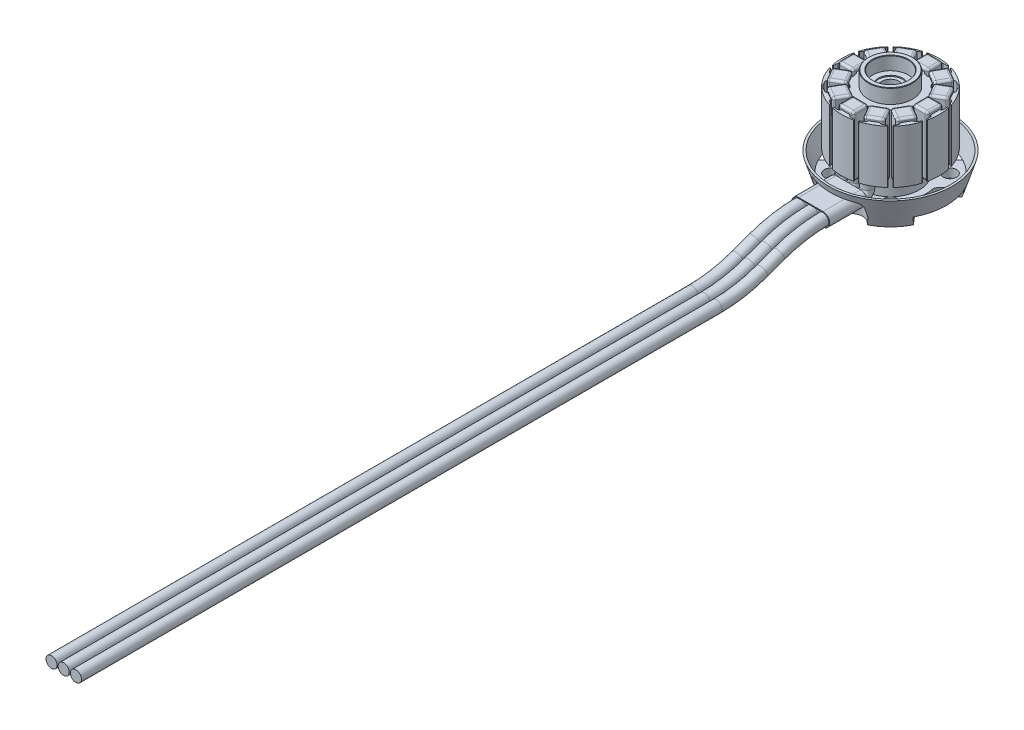
SolidWorks part; units mm, degrees
ref_plane "Front Plane" through (0, 0, 0) normal (0, 0, 1) x (1, 0, 0)
ref_plane "Top Plane" through (0, 0, 0) normal (0, 1, 0) x (1, 0, 0)
ref_plane "Right Plane" through (0, 0, 0) normal (1, 0, 0) x (0, 0, -1)
ref_plane "Plane6" through (0, 0, 15.3597) normal (0, 0, 1) x (1, 0, 0)
sketch "Sketch1" plane through (0, 0, 0) normal (0, 0, 1) x (1, 0, 0)
  line L0 (4, 0) -> (12, 0)
  line L1 (12, 0) -> (14, 6.5)
  line L2 (14, 6.5) -> (13.5, 6.5)
  line L3 (4, 0) -> (4, 3)
  line L4 (2, 3.35) -> (2.1, 3.25)
  line L5 (5, 7) -> (5, 22.15)
  line L6 (6.5, 2) -> (12.1154, 2)
  line L7 (13.5, 6.5) -> (12.1154, 2)
  line L14 (4.9, 22.25) -> (4.1, 22.25)
  line L15 (4, 22.15) -> (4, 19.25)
  line L16 (4, 19.25) -> (2.75, 19.25)
  line L17 (2, 3.35) -> (2, 19)
  line L18 (0, -5) -> (0, 30) construction
  line L19 (2.1, 3.25) -> (2.75, 3.25)
  line L20 (4.1, 22.25) -> (4, 22.15)
  line L21 (5, 22.15) -> (4.9, 22.25)
  line L23 (2.85, 3) -> (4, 3)
  line L24 (2, 19) -> (2.75, 19)
  line L25 (5, 7) -> (6.5, 7)
  line L26 (6.5, 7) -> (6.5, 2)
  line L27 (2.75, 19) -> (2.75, 19.25)
  line L28 (2.75, 3.25) -> (2.75, 3.1)
  line L29 (2.75, 3.1) -> (2.85, 3)
  point P9 (5, 22.25)
  point P22 (4, 22.25)
  point P24 (2, 3.25)
  point P44 (2.75, 3)
revolve "Revolve1" add sketch "Sketch1" angle 360 about L18
ref_plane "Plane1" through (0, 0, 15) normal (0, 0, 1) x (1, 0, 0)
sketch "Sketch5" plane through (0, 7, 0) normal (0, 1, 0) x (1, 0, 0)
  line L0 (-1, 9.8636) -> (-1, 7.3485)
  line L1 (0, 0) -> (0, 14) construction
  line L2 (-2.2472, 10.3636) -> (-1.5, 10.3636)
  line L3 (2.2472, 10.3636) -> (1.5, 10.3636)
  line L4 (1, 9.8636) -> (1, 7.3485)
  line L5 (7.1279, 7.8516) -> (6.4808, 8.2252)
  line L6 (5.7978, 8.0421) -> (4.5403, 5.864)
  line L7 (4.0658, 9.0421) -> (2.8082, 6.864)
  line L8 (3.2357, 10.0988) -> (3.8828, 9.7252)
  line L9 (10.0988, 3.2357) -> (9.7252, 3.8828)
  line L10 (9.0421, 4.0658) -> (6.864, 2.8082)
  line L11 (8.0421, 5.7978) -> (5.864, 4.5403)
  line L12 (7.8516, 7.1279) -> (8.2252, 6.4808)
  line L13 (10.3636, -2.2472) -> (10.3636, -1.5)
  line L14 (9.8636, -1) -> (7.3485, -1)
  line L15 (9.8636, 1) -> (7.3485, 1)
  line L16 (10.3636, 2.2472) -> (10.3636, 1.5)
  line L17 (7.8516, -7.1279) -> (8.2252, -6.4808)
  line L18 (8.0421, -5.7978) -> (5.864, -4.5403)
  line L19 (9.0421, -4.0658) -> (6.864, -2.8082)
  line L20 (10.0988, -3.2357) -> (9.7252, -3.8828)
  line L21 (3.2357, -10.0988) -> (3.8828, -9.7252)
  line L22 (4.0658, -9.0421) -> (2.8082, -6.864)
  line L23 (5.7978, -8.0421) -> (4.5403, -5.864)
  line L24 (7.1279, -7.8516) -> (6.4808, -8.2252)
  line L25 (-2.2472, -10.3636) -> (-1.5, -10.3636)
  line L26 (-1, -9.8636) -> (-1, -7.3485)
  line L27 (1, -9.8636) -> (1, -7.3485)
  line L28 (2.2472, -10.3636) -> (1.5, -10.3636)
  line L29 (-7.1279, -7.8516) -> (-6.4808, -8.2252)
  line L30 (-5.7978, -8.0421) -> (-4.5403, -5.864)
  line L31 (-4.0658, -9.0421) -> (-2.8082, -6.864)
  line L32 (-3.2357, -10.0988) -> (-3.8828, -9.7252)
  line L33 (-10.0988, -3.2357) -> (-9.7252, -3.8828)
  line L34 (-9.0421, -4.0658) -> (-6.864, -2.8082)
  line L35 (-8.0421, -5.7978) -> (-5.864, -4.5403)
  line L36 (-7.8516, -7.1279) -> (-8.2252, -6.4808)
  line L37 (-10.3636, 2.2472) -> (-10.3636, 1.5)
  line L38 (-9.8636, 1) -> (-7.3485, 1)
  line L39 (-9.8636, -1) -> (-7.3485, -1)
  line L40 (-10.3636, -2.2472) -> (-10.3636, -1.5)
  line L41 (-7.8516, 7.1279) -> (-8.2252, 6.4808)
  line L42 (-8.0421, 5.7978) -> (-5.864, 4.5403)
  line L43 (-9.0421, 4.0658) -> (-6.864, 2.8082)
  line L44 (-10.0988, 3.2357) -> (-9.7252, 3.8828)
  line L45 (-3.2357, 10.0988) -> (-3.8828, 9.7252)
  line L46 (-4.0658, 9.0421) -> (-2.8082, 6.864)
  line L47 (-5.7978, 8.0421) -> (-4.5403, 5.864)
  line L48 (-7.1279, 7.8516) -> (-6.4808, 8.2252)
  circle A0 centre (0, 0) radius 5
  arc A1 (2.2888, 10.7592) -> (-2.2888, 10.7592) centre (0, 0) ccw
  arc A2 (-1.4, 6.8586) -> (-2.2169, 6.6397) centre (0, 0) ccw
  arc A3 (-2.2472, 10.3636) -> (-2.2888, 10.7592) centre (-2.2472, 10.5636) cw
  arc A4 (-1.5, 10.3636) -> (-1, 9.8636) centre (-1.5, 9.8636) cw
  arc A5 (-1, 7.3485) -> (-1.4, 6.8586) centre (-1.5, 7.3485) cw
  arc A6 (2.2472, 10.3636) -> (2.2888, 10.7592) centre (2.2472, 10.5636) ccw
  arc A7 (1.5, 10.3636) -> (1, 9.8636) centre (1.5, 9.8636) ccw
  arc A8 (1, 7.3485) -> (1.4, 6.8586) centre (1.5, 7.3485) ccw
  arc A9 (7.3618, 8.1734) -> (3.3975, 10.4622) centre (0, 0) ccw
  arc A10 (6.4808, 8.2252) -> (5.7978, 8.0421) centre (6.2308, 7.7921) ccw
  arc A11 (7.1279, 7.8516) -> (7.3618, 8.1734) centre (7.2279, 8.0248) ccw
  arc A12 (4.5403, 5.864) -> (4.6417, 5.2397) centre (4.9733, 5.614) ccw
  arc A13 (2.8082, 6.864) -> (2.2169, 6.6397) centre (2.3752, 7.114) cw
  arc A14 (3.8828, 9.7252) -> (4.0658, 9.0421) centre (3.6328, 9.2921) cw
  arc A15 (3.2357, 10.0988) -> (3.3975, 10.4622) centre (3.3357, 10.272) cw
  arc A16 (10.4622, 3.3975) -> (8.1734, 7.3618) centre (0, 0) ccw
  arc A17 (9.7252, 3.8828) -> (9.0421, 4.0658) centre (9.2921, 3.6328) ccw
  arc A18 (10.0988, 3.2357) -> (10.4622, 3.3975) centre (10.272, 3.3357) ccw
  arc A19 (6.864, 2.8082) -> (6.6397, 2.2169) centre (7.114, 2.3752) ccw
  arc A20 (5.864, 4.5403) -> (5.2397, 4.6417) centre (5.614, 4.9733) cw
  arc A21 (8.2252, 6.4808) -> (8.0421, 5.7978) centre (7.7921, 6.2308) cw
  arc A22 (7.8516, 7.1279) -> (8.1734, 7.3618) centre (8.0248, 7.2279) cw
  arc A23 (10.7592, -2.2888) -> (10.7592, 2.2888) centre (0, 0) ccw
  arc A24 (10.3636, -1.5) -> (9.8636, -1) centre (9.8636, -1.5) ccw
  arc A25 (10.3636, -2.2472) -> (10.7592, -2.2888) centre (10.5636, -2.2472) ccw
  arc A26 (7.3485, -1) -> (6.8586, -1.4) centre (7.3485, -1.5) ccw
  arc A27 (7.3485, 1) -> (6.8586, 1.4) centre (7.3485, 1.5) cw
  arc A28 (10.3636, 1.5) -> (9.8636, 1) centre (9.8636, 1.5) cw
  arc A29 (10.3636, 2.2472) -> (10.7592, 2.2888) centre (10.5636, 2.2472) cw
  arc A30 (8.1734, -7.3618) -> (10.4622, -3.3975) centre (0, 0) ccw
  arc A31 (8.2252, -6.4808) -> (8.0421, -5.7978) centre (7.7921, -6.2308) ccw
  arc A32 (7.8516, -7.1279) -> (8.1734, -7.3618) centre (8.0248, -7.2279) ccw
  arc A33 (5.864, -4.5403) -> (5.2397, -4.6417) centre (5.614, -4.9733) ccw
  arc A34 (6.864, -2.8082) -> (6.6397, -2.2169) centre (7.114, -2.3752) cw
  arc A35 (9.7252, -3.8828) -> (9.0421, -4.0658) centre (9.2921, -3.6328) cw
  arc A36 (10.0988, -3.2357) -> (10.4622, -3.3975) centre (10.272, -3.3357) cw
  arc A37 (3.3975, -10.4622) -> (7.3618, -8.1734) centre (0, 0) ccw
  arc A38 (3.8828, -9.7252) -> (4.0658, -9.0421) centre (3.6328, -9.2921) ccw
  arc A39 (3.2357, -10.0988) -> (3.3975, -10.4622) centre (3.3357, -10.272) ccw
  arc A40 (2.8082, -6.864) -> (2.2169, -6.6397) centre (2.3752, -7.114) ccw
  arc A41 (4.5403, -5.864) -> (4.6417, -5.2397) centre (4.9733, -5.614) cw
  arc A42 (6.4808, -8.2252) -> (5.7978, -8.0421) centre (6.2308, -7.7921) cw
  arc A43 (7.1279, -7.8516) -> (7.3618, -8.1734) centre (7.2279, -8.0248) cw
  arc A44 (-2.2888, -10.7592) -> (2.2888, -10.7592) centre (0, 0) ccw
  arc A45 (-1.5, -10.3636) -> (-1, -9.8636) centre (-1.5, -9.8636) ccw
  arc A46 (-2.2472, -10.3636) -> (-2.2888, -10.7592) centre (-2.2472, -10.5636) ccw
  arc A47 (-1, -7.3485) -> (-1.4, -6.8586) centre (-1.5, -7.3485) ccw
  arc A48 (1, -7.3485) -> (1.4, -6.8586) centre (1.5, -7.3485) cw
  arc A49 (1.5, -10.3636) -> (1, -9.8636) centre (1.5, -9.8636) cw
  arc A50 (2.2472, -10.3636) -> (2.2888, -10.7592) centre (2.2472, -10.5636) cw
  arc A51 (-7.3618, -8.1734) -> (-3.3975, -10.4622) centre (0, 0) ccw
  arc A52 (-6.4808, -8.2252) -> (-5.7978, -8.0421) centre (-6.2308, -7.7921) ccw
  arc A53 (-7.1279, -7.8516) -> (-7.3618, -8.1734) centre (-7.2279, -8.0248) ccw
  arc A54 (-4.5403, -5.864) -> (-4.6417, -5.2397) centre (-4.9733, -5.614) ccw
  arc A55 (-2.8082, -6.864) -> (-2.2169, -6.6397) centre (-2.3752, -7.114) cw
  arc A56 (-3.8828, -9.7252) -> (-4.0658, -9.0421) centre (-3.6328, -9.2921) cw
  arc A57 (-3.2357, -10.0988) -> (-3.3975, -10.4622) centre (-3.3357, -10.272) cw
  arc A58 (-10.4622, -3.3975) -> (-8.1734, -7.3618) centre (0, 0) ccw
  arc A59 (-9.7252, -3.8828) -> (-9.0421, -4.0658) centre (-9.2921, -3.6328) ccw
  arc A60 (-10.0988, -3.2357) -> (-10.4622, -3.3975) centre (-10.272, -3.3357) ccw
  arc A61 (-6.864, -2.8082) -> (-6.6397, -2.2169) centre (-7.114, -2.3752) ccw
  arc A62 (-5.864, -4.5403) -> (-5.2397, -4.6417) centre (-5.614, -4.9733) cw
  arc A63 (-8.2252, -6.4808) -> (-8.0421, -5.7978) centre (-7.7921, -6.2308) cw
  arc A64 (-7.8516, -7.1279) -> (-8.1734, -7.3618) centre (-8.0248, -7.2279) cw
  arc A65 (-10.7592, 2.2888) -> (-10.7592, -2.2888) centre (0, 0) ccw
  arc A66 (-10.3636, 1.5) -> (-9.8636, 1) centre (-9.8636, 1.5) ccw
  arc A67 (-10.3636, 2.2472) -> (-10.7592, 2.2888) centre (-10.5636, 2.2472) ccw
  arc A68 (-7.3485, 1) -> (-6.8586, 1.4) centre (-7.3485, 1.5) ccw
  arc A69 (-7.3485, -1) -> (-6.8586, -1.4) centre (-7.3485, -1.5) cw
  arc A70 (-10.3636, -1.5) -> (-9.8636, -1) centre (-9.8636, -1.5) cw
  arc A71 (-10.3636, -2.2472) -> (-10.7592, -2.2888) centre (-10.5636, -2.2472) cw
  arc A72 (-8.1734, 7.3618) -> (-10.4622, 3.3975) centre (0, 0) ccw
  arc A73 (-8.2252, 6.4808) -> (-8.0421, 5.7978) centre (-7.7921, 6.2308) ccw
  arc A74 (-7.8516, 7.1279) -> (-8.1734, 7.3618) centre (-8.0248, 7.2279) ccw
  arc A75 (-5.864, 4.5403) -> (-5.2397, 4.6417) centre (-5.614, 4.9733) ccw
  arc A76 (-6.864, 2.8082) -> (-6.6397, 2.2169) centre (-7.114, 2.3752) cw
  arc A77 (-9.7252, 3.8828) -> (-9.0421, 4.0658) centre (-9.2921, 3.6328) cw
  arc A78 (-10.0988, 3.2357) -> (-10.4622, 3.3975) centre (-10.272, 3.3357) cw
  arc A79 (-3.3975, 10.4622) -> (-7.3618, 8.1734) centre (0, 0) ccw
  arc A80 (-3.8828, 9.7252) -> (-4.0658, 9.0421) centre (-3.6328, 9.2921) ccw
  arc A81 (-3.2357, 10.0988) -> (-3.3975, 10.4622) centre (-3.3357, 10.272) ccw
  arc A82 (-2.8082, 6.864) -> (-2.2169, 6.6397) centre (-2.3752, 7.114) ccw
  arc A83 (-4.5403, 5.864) -> (-4.6417, 5.2397) centre (-4.9733, 5.614) cw
  arc A84 (-6.4808, 8.2252) -> (-5.7978, 8.0421) centre (-6.2308, 7.7921) cw
  arc A85 (-7.1279, 7.8516) -> (-7.3618, 8.1734) centre (-7.2279, 8.0248) cw
  arc A86 (-4.6417, 5.2397) -> (-5.2397, 4.6417) centre (0, 0) ccw
  arc A87 (2.2169, 6.6397) -> (1.4, 6.8586) centre (0, 0) ccw
  arc A88 (5.2397, 4.6417) -> (4.6417, 5.2397) centre (0, 0) ccw
  arc A89 (6.8586, 1.4) -> (6.6397, 2.2169) centre (0, 0) ccw
  arc A90 (6.6397, -2.2169) -> (6.8586, -1.4) centre (0, 0) ccw
  arc A91 (-6.6397, 2.2169) -> (-6.8586, 1.4) centre (0, 0) ccw
  arc A92 (-6.8586, -1.4) -> (-6.6397, -2.2169) centre (0, 0) ccw
  arc A93 (-5.2397, -4.6417) -> (-4.6417, -5.2397) centre (0, 0) ccw
  arc A94 (-2.2169, -6.6397) -> (-1.4, -6.8586) centre (0, 0) ccw
  arc A95 (1.4, -6.8586) -> (2.2169, -6.6397) centre (0, 0) ccw
  arc A96 (4.6417, -5.2397) -> (5.2397, -4.6417) centre (0, 0) ccw
  point P223 (0, 0)
  dimension "D1" = 22
  dimension "D2" = 0.2
  dimension "D3" = 0.5
  dimension "D4" = 7
  dimension "D7" = 10
  dimension "D5" = 1
  dimension "D6" = 12
sketch "Sketch6" plane through (0, 0, 0) normal (0, -1, 0) x (1, 0, 0)
  line L0 (-14.1421, 14.1421) -> (0, 0) construction
  line L1 (0, 0) -> (14.1421, 14.1421) construction
  line L2 (0, 0) -> (0, 28.2843) construction
  line L3 (-7.1141, 12.0577) -> (-4.8767, 10.14)
  line L4 (7.1141, 12.0577) -> (4.8767, 10.14)
  line L5 (12.0577, 7.1141) -> (8.0592, 2.4492)
  line L6 (12.0577, -7.1141) -> (8.0592, -2.4492)
  line L7 (7.1141, -12.0577) -> (2.4492, -8.0592)
  line L8 (-7.1141, -12.0577) -> (-2.4492, -8.0592)
  line L9 (-12.0577, -7.1141) -> (-8.0592, -2.4492)
  line L10 (-12.0577, 7.1141) -> (-8.0592, 2.4492)
  line L11 (0, 12) -> (-0.7499, 12.0123)
  line L12 (0, 12) -> (0.7499, 12.0123)
  arc A0 (-12.0577, 7.1141) -> (-12.0577, -7.1141) centre (0, 0) ccw
  arc A1 (-1.5986, -7.8387) -> (1.5986, -7.8387) centre (0, 0) ccw
  arc A2 (12.0577, -7.1141) -> (12.0577, 7.1141) centre (0, 0) ccw
  arc A3 (-7.1141, -12.0577) -> (7.1141, -12.0577) centre (0, 0) ccw
  arc A4 (-7.8387, 1.5986) -> (-7.8387, -1.5986) centre (0, 0) ccw
  arc A6 (7.8387, -1.5986) -> (7.8387, 1.5986) centre (0, 0) ccw
  arc A7 (7.1141, 12.0577) -> (-7.1141, 12.0577) centre (0, 0) ccw
  circle A8 centre (-6.7175, 6.7175) radius 1.5
  circle A9 centre (5.6569, 5.6569) radius 1.5
  circle A10 centre (6.7175, -6.7175) radius 1.5
  circle A11 centre (-5.6569, -5.6569) radius 1.5
  arc A12 (-2.4492, -8.0592) -> (-1.5986, -7.8387) centre (-1.7984, -8.8185) cw
  arc A13 (2.4492, -8.0592) -> (1.5986, -7.8387) centre (1.7984, -8.8185) ccw
  arc A14 (8.0592, -2.4492) -> (7.8387, -1.5986) centre (8.8185, -1.7984) cw
  arc A15 (8.0592, 2.4492) -> (7.8387, 1.5986) centre (8.8185, 1.7984) ccw
  arc A17 (4.8767, 10.14) -> (0.7499, 12.0123) centre (3.2498, 12.0381) cw
  arc A18 (-8.0592, 2.4492) -> (-7.8387, 1.5986) centre (-8.8185, 1.7984) cw
  arc A19 (-8.0592, -2.4492) -> (-7.8387, -1.5986) centre (-8.8185, -1.7984) ccw
  arc A20 (-4.8767, 10.14) -> (-0.7499, 12.0123) centre (-3.2498, 12.0381) ccw
  point P20 (0, 0)
  point P39 (2.0641, 7.7291)
  point P42 (-2.0641, 7.7291)
  dimension "D1" = 28
  dimension "D2" = 16
  dimension "D3" = 3
  dimension "D4" = 3
  dimension "D7" = 1
  dimension "D8" = 5
  dimension "D5" = 9.5
  dimension "D6" = 8
  dimension "D9" = 0.75
extrude "Cut-Extrude1" cut sketch "Sketch6" against normal blind 2
ref_axis "Axis2" through (0, 19, 0) along (0, -1, 0)
sketch "Sketch10" plane through (6.2132, 0, 15.3597) normal (0, 0, 1) x (1, 0, 0)
  line L0 (-12.2092, 2) -> (-0.2172, 2) construction
  line L1 (-12.2092, 2) -> (-0.2172, 2)
  line L2 (-12.2092, 2) -> (-12.2092, 4)
  line L3 (-11.2092, 5) -> (-1.2172, 5)
  line L4 (-0.2172, 4) -> (-0.2172, 2)
  arc A0 (-1.2172, 5) -> (-0.2172, 4) centre (-1.2172, 4) cw
  arc A1 (-12.2092, 4) -> (-11.2092, 5) centre (-11.2092, 4) cw
  dimension "D1" = 1
extrude "Cut-Extrude3" cut sketch "Sketch10" against normal blind 5 contours L1 L4 A0 L3 A1 L2
sketch "Sketch11" plane through (0, 7, 0) normal (0, 1, 0) x (1, 0, 0)
  line L0 (-1, 10) -> (-1, 6.8374)
  line L1 (-2.3184, 10.5) -> (-1.5, 10.5)
  line L2 (0, 20) -> (0, 0) construction
  line L3 (0, 0) -> (20, 0) construction
  line L4 (2.3184, 10.5) -> (1.5, 10.5)
  line L5 (1, 10) -> (1, 6.8374)
  line L6 (3.2422, 10.2525) -> (3.951, 9.8433)
  line L7 (4.134, 9.1603) -> (2.5527, 6.4214)
  line L8 (5.866, 8.1603) -> (4.2847, 5.4214)
  line L9 (7.2578, 7.9341) -> (6.549, 8.3433)
  line L10 (7.9341, 7.2578) -> (8.3433, 6.549)
  line L11 (8.1603, 5.866) -> (5.4214, 4.2847)
  line L12 (9.1603, 4.134) -> (6.4214, 2.5527)
  line L13 (10.2525, 3.2422) -> (9.8433, 3.951)
  line L14 (10.5, 2.3184) -> (10.5, 1.5)
  line L15 (10, 1) -> (6.8374, 1)
  line L16 (10, -1) -> (6.8374, -1)
  line L17 (10.5, -2.3184) -> (10.5, -1.5)
  line L18 (10.2525, -3.2422) -> (9.8433, -3.951)
  line L19 (9.1603, -4.134) -> (6.4214, -2.5527)
  line L20 (8.1603, -5.866) -> (5.4214, -4.2847)
  line L21 (7.9341, -7.2578) -> (8.3433, -6.549)
  line L22 (7.2578, -7.9341) -> (6.549, -8.3433)
  line L23 (5.866, -8.1603) -> (4.2847, -5.4214)
  line L24 (4.134, -9.1603) -> (2.5527, -6.4214)
  line L25 (3.2422, -10.2525) -> (3.951, -9.8433)
  line L26 (2.3184, -10.5) -> (1.5, -10.5)
  line L27 (1, -10) -> (1, -6.8374)
  line L28 (-1, -10) -> (-1, -6.8374)
  line L29 (-2.3184, -10.5) -> (-1.5, -10.5)
  line L30 (-3.2422, -10.2525) -> (-3.951, -9.8433)
  line L31 (-4.134, -9.1603) -> (-2.5527, -6.4214)
  line L32 (-5.866, -8.1603) -> (-4.2847, -5.4214)
  line L33 (-7.2578, -7.9341) -> (-6.549, -8.3433)
  line L34 (-7.9341, -7.2578) -> (-8.3433, -6.549)
  line L35 (-8.1603, -5.866) -> (-5.4214, -4.2847)
  line L36 (-9.1603, -4.134) -> (-6.4214, -2.5527)
  line L37 (-10.2525, -3.2422) -> (-9.8433, -3.951)
  line L38 (-10.5, -2.3184) -> (-10.5, -1.5)
  line L39 (-10, -1) -> (-6.8374, -1)
  line L40 (-10, 1) -> (-6.8374, 1)
  line L41 (-10.5, 2.3184) -> (-10.5, 1.5)
  line L42 (-10.2525, 3.2422) -> (-9.8433, 3.951)
  line L43 (-9.1603, 4.134) -> (-6.4214, 2.5527)
  line L44 (-8.1603, 5.866) -> (-5.4214, 4.2847)
  line L45 (-7.9341, 7.2578) -> (-8.3433, 6.549)
  line L46 (-7.2578, 7.9341) -> (-6.549, 8.3433)
  line L47 (-5.866, 8.1603) -> (-4.2847, 5.4214)
  line L48 (-4.134, 9.1603) -> (-2.5527, 6.4214)
  line L49 (-3.2422, 10.2525) -> (-3.951, 9.8433)
  circle A0 centre (0, 0) radius 5
  arc A1 (2.3451, 10.7471) -> (-2.3451, 10.7471) centre (0, 0) ccw
  arc A2 (-1.3929, 6.349) -> (-1.9683, 6.1948) centre (0, 0) ccw
  arc A3 (2.3184, 10.5) -> (2.3451, 10.7471) centre (2.3184, 10.625) ccw
  arc A4 (-2.3184, 10.5) -> (-2.3451, 10.7471) centre (-2.3184, 10.625) cw
  arc A5 (1.5, 10.5) -> (1, 10) centre (1.5, 10) ccw
  arc A6 (-1, 10) -> (-1.5, 10.5) centre (-1.5, 10) ccw
  arc A7 (1, 6.8374) -> (1.3929, 6.349) centre (1.5, 6.8374) ccw
  arc A8 (-1, 6.8374) -> (-1.3929, 6.349) centre (-1.5, 6.8374) cw
  arc A9 (7.4044, 8.1348) -> (3.3427, 10.4798) centre (0, 0) ccw
  arc A10 (3.2422, 10.2525) -> (3.3427, 10.4798) centre (3.3047, 10.3607) cw
  arc A11 (4.134, 9.1603) -> (3.951, 9.8433) centre (3.701, 9.4103) ccw
  arc A12 (2.5527, 6.4214) -> (1.9683, 6.1948) centre (2.1197, 6.6714) cw
  arc A13 (4.2847, 5.4214) -> (4.3808, 4.802) centre (4.7177, 5.1714) ccw
  arc A14 (6.549, 8.3433) -> (5.866, 8.1603) centre (6.299, 7.9103) ccw
  arc A15 (7.2578, 7.9341) -> (7.4044, 8.1348) centre (7.3203, 8.0423) ccw
  arc A16 (10.4798, 3.3427) -> (8.1348, 7.4044) centre (0, 0) ccw
  arc A17 (7.9341, 7.2578) -> (8.1348, 7.4044) centre (8.0423, 7.3203) cw
  arc A18 (8.1603, 5.866) -> (8.3433, 6.549) centre (7.9103, 6.299) ccw
  arc A19 (5.4214, 4.2847) -> (4.802, 4.3808) centre (5.1714, 4.7177) cw
  arc A20 (6.4214, 2.5527) -> (6.1948, 1.9683) centre (6.6714, 2.1197) ccw
  arc A21 (9.8433, 3.951) -> (9.1603, 4.134) centre (9.4103, 3.701) ccw
  arc A22 (10.2525, 3.2422) -> (10.4798, 3.3427) centre (10.3607, 3.3047) ccw
  arc A23 (10.7471, -2.3451) -> (10.7471, 2.3451) centre (0, 0) ccw
  arc A24 (10.5, 2.3184) -> (10.7471, 2.3451) centre (10.625, 2.3184) cw
  arc A25 (10, 1) -> (10.5, 1.5) centre (10, 1.5) ccw
  arc A26 (6.8374, 1) -> (6.349, 1.3929) centre (6.8374, 1.5) cw
  arc A27 (6.8374, -1) -> (6.349, -1.3929) centre (6.8374, -1.5) ccw
  arc A28 (10.5, -1.5) -> (10, -1) centre (10, -1.5) ccw
  arc A29 (10.5, -2.3184) -> (10.7471, -2.3451) centre (10.625, -2.3184) ccw
  arc A30 (8.1348, -7.4044) -> (10.4798, -3.3427) centre (0, 0) ccw
  arc A31 (10.2525, -3.2422) -> (10.4798, -3.3427) centre (10.3607, -3.3047) cw
  arc A32 (9.1603, -4.134) -> (9.8433, -3.951) centre (9.4103, -3.701) ccw
  arc A33 (6.4214, -2.5527) -> (6.1948, -1.9683) centre (6.6714, -2.1197) cw
  arc A34 (5.4214, -4.2847) -> (4.802, -4.3808) centre (5.1714, -4.7177) ccw
  arc A35 (8.3433, -6.549) -> (8.1603, -5.866) centre (7.9103, -6.299) ccw
  arc A36 (7.9341, -7.2578) -> (8.1348, -7.4044) centre (8.0423, -7.3203) ccw
  arc A37 (3.3427, -10.4798) -> (7.4044, -8.1348) centre (0, 0) ccw
  arc A38 (7.2578, -7.9341) -> (7.4044, -8.1348) centre (7.3203, -8.0423) cw
  arc A39 (5.866, -8.1603) -> (6.549, -8.3433) centre (6.299, -7.9103) ccw
  arc A40 (4.2847, -5.4214) -> (4.3808, -4.802) centre (4.7177, -5.1714) cw
  arc A41 (2.5527, -6.4214) -> (1.9683, -6.1948) centre (2.1197, -6.6714) ccw
  arc A42 (3.951, -9.8433) -> (4.134, -9.1603) centre (3.701, -9.4103) ccw
  arc A43 (3.2422, -10.2525) -> (3.3427, -10.4798) centre (3.3047, -10.3607) ccw
  arc A44 (-2.3451, -10.7471) -> (2.3451, -10.7471) centre (0, 0) ccw
  arc A45 (2.3184, -10.5) -> (2.3451, -10.7471) centre (2.3184, -10.625) cw
  arc A46 (1, -10) -> (1.5, -10.5) centre (1.5, -10) ccw
  arc A47 (1, -6.8374) -> (1.3929, -6.349) centre (1.5, -6.8374) cw
  arc A48 (-1, -6.8374) -> (-1.3929, -6.349) centre (-1.5, -6.8374) ccw
  arc A49 (-1.5, -10.5) -> (-1, -10) centre (-1.5, -10) ccw
  arc A50 (-2.3184, -10.5) -> (-2.3451, -10.7471) centre (-2.3184, -10.625) ccw
  arc A51 (-7.4044, -8.1348) -> (-3.3427, -10.4798) centre (0, 0) ccw
  arc A52 (-3.2422, -10.2525) -> (-3.3427, -10.4798) centre (-3.3047, -10.3607) cw
  arc A53 (-4.134, -9.1603) -> (-3.951, -9.8433) centre (-3.701, -9.4103) ccw
  arc A54 (-2.5527, -6.4214) -> (-1.9683, -6.1948) centre (-2.1197, -6.6714) cw
  arc A55 (-4.2847, -5.4214) -> (-4.3808, -4.802) centre (-4.7177, -5.1714) ccw
  arc A56 (-6.549, -8.3433) -> (-5.866, -8.1603) centre (-6.299, -7.9103) ccw
  arc A57 (-7.2578, -7.9341) -> (-7.4044, -8.1348) centre (-7.3203, -8.0423) ccw
  arc A58 (-10.4798, -3.3427) -> (-8.1348, -7.4044) centre (0, 0) ccw
  arc A59 (-7.9341, -7.2578) -> (-8.1348, -7.4044) centre (-8.0423, -7.3203) cw
  arc A60 (-8.1603, -5.866) -> (-8.3433, -6.549) centre (-7.9103, -6.299) ccw
  arc A61 (-5.4214, -4.2847) -> (-4.802, -4.3808) centre (-5.1714, -4.7177) cw
  arc A62 (-6.4214, -2.5527) -> (-6.1948, -1.9683) centre (-6.6714, -2.1197) ccw
  arc A63 (-9.8433, -3.951) -> (-9.1603, -4.134) centre (-9.4103, -3.701) ccw
  arc A64 (-10.2525, -3.2422) -> (-10.4798, -3.3427) centre (-10.3607, -3.3047) ccw
  arc A65 (-10.7471, 2.3451) -> (-10.7471, -2.3451) centre (0, 0) ccw
  arc A66 (-10.5, -2.3184) -> (-10.7471, -2.3451) centre (-10.625, -2.3184) cw
  arc A67 (-10, -1) -> (-10.5, -1.5) centre (-10, -1.5) ccw
  arc A68 (-6.8374, -1) -> (-6.349, -1.3929) centre (-6.8374, -1.5) cw
  arc A69 (-6.8374, 1) -> (-6.349, 1.3929) centre (-6.8374, 1.5) ccw
  arc A70 (-10.5, 1.5) -> (-10, 1) centre (-10, 1.5) ccw
  arc A71 (-10.5, 2.3184) -> (-10.7471, 2.3451) centre (-10.625, 2.3184) ccw
  arc A72 (-8.1348, 7.4044) -> (-10.4798, 3.3427) centre (0, 0) ccw
  arc A73 (-10.2525, 3.2422) -> (-10.4798, 3.3427) centre (-10.3607, 3.3047) cw
  arc A74 (-9.1603, 4.134) -> (-9.8433, 3.951) centre (-9.4103, 3.701) ccw
  arc A75 (-6.4214, 2.5527) -> (-6.1948, 1.9683) centre (-6.6714, 2.1197) cw
  arc A76 (-5.4214, 4.2847) -> (-4.802, 4.3808) centre (-5.1714, 4.7177) ccw
  arc A77 (-8.3433, 6.549) -> (-8.1603, 5.866) centre (-7.9103, 6.299) ccw
  arc A78 (-7.9341, 7.2578) -> (-8.1348, 7.4044) centre (-8.0423, 7.3203) ccw
  arc A79 (-3.3427, 10.4798) -> (-7.4044, 8.1348) centre (0, 0) ccw
  arc A80 (-7.2578, 7.9341) -> (-7.4044, 8.1348) centre (-7.3203, 8.0423) cw
  arc A81 (-5.866, 8.1603) -> (-6.549, 8.3433) centre (-6.299, 7.9103) ccw
  arc A82 (-4.2847, 5.4214) -> (-4.3808, 4.802) centre (-4.7177, 5.1714) cw
  arc A83 (-2.5527, 6.4214) -> (-1.9683, 6.1948) centre (-2.1197, 6.6714) ccw
  arc A84 (-3.951, 9.8433) -> (-4.134, 9.1603) centre (-3.701, 9.4103) ccw
  arc A85 (-3.2422, 10.2525) -> (-3.3427, 10.4798) centre (-3.3047, 10.3607) ccw
  arc A86 (1.9683, 6.1948) -> (1.3929, 6.349) centre (0, 0) ccw
  arc A87 (4.802, 4.3808) -> (4.3808, 4.802) centre (0, 0) ccw
  arc A88 (6.349, 1.3929) -> (6.1948, 1.9683) centre (0, 0) ccw
  arc A89 (6.1948, -1.9683) -> (6.349, -1.3929) centre (0, 0) ccw
  arc A90 (4.3808, -4.802) -> (4.802, -4.3808) centre (0, 0) ccw
  arc A91 (1.3929, -6.349) -> (1.9683, -6.1948) centre (0, 0) ccw
  arc A92 (-1.9683, -6.1948) -> (-1.3929, -6.349) centre (0, 0) ccw
  arc A93 (-4.802, -4.3808) -> (-4.3808, -4.802) centre (0, 0) ccw
  arc A94 (-6.349, -1.3929) -> (-6.1948, -1.9683) centre (0, 0) ccw
  arc A95 (-6.1948, 1.9683) -> (-6.349, 1.3929) centre (0, 0) ccw
  arc A96 (-4.3808, 4.802) -> (-4.802, 4.3808) centre (0, 0) ccw
  point P13 (3.2787, 10.5)
  point P16 (-3.2787, 10.5)
  point P19 (1, 10.5)
  point P22 (-1, 10.5)
  point P25 (1, 6.4226)
  point P28 (-1, 6.4226)
  point P230 (0, 0)
  dimension "D1" = 22
  dimension "D2" = 0.125
  dimension "D3" = 0.5
  dimension "D4" = 6.5
  dimension "D6" = 2
  dimension "D5" = 12
extrude "Boss-Extrude2" add sketch "Sketch11" along normal blind 12 separate body
ref_plane "Plane7" through (0, 0, 6.7) normal (0, 0, 1) x (1, 0, 0)
sketch "Sketch12" plane through (0, 0, 6.7) normal (0, 0, 1) x (1, 0, 0)
  line L0 (1, 19) -> (1, 7) construction
  line L1 (-1, 19) -> (-1, 7) construction
  line L2 (1, 19) -> (1, 7)
  line L3 (-1, 19) -> (-1, 7)
  line L4 (-1, 19) -> (1, 19)
  line L5 (-1, 7) -> (1, 7)
  line L6 (-1.78, 19.78) -> (1.78, 19.78)
  line L7 (1.78, 19.78) -> (1.78, 6.22)
  line L8 (-1.78, 6.22) -> (1.78, 6.22)
  line L9 (-1.78, 19.78) -> (-1.78, 6.22)
  dimension "D1" = 0.78
extrude "Boss-Extrude3" add sketch "Sketch12" along normal blind 3.4
fillet "Fillet2" radius 0.5 12 edges at (-1.78, 6.22, 8.4) (0, 6.22, 10.1) (1.78, 6.22, 8.4) (0, 6.22, 6.7) (1.78, 19.78, 8.4) (0, 19.78, 10.1) (-1.78, 19.78, 8.4) (0, 19.78, 6.7) (-1.78, 13, 6.7) (-1.78, 13, 10.1) (1.78, 13, 6.7) (1.78, 13, 10.1)
pattern_circular "CirPattern3" count 12 over 360 about axis through (0, 19, 0) along (0, -1, 0) of "Boss-Extrude3", "Fillet2"
ref_plane "Plane8" through (0, 6, 0) normal (0, 1, 0) x (1, 0, 0)
sketch "Sketch13" plane through (0, 6, 0) normal (0, 1, 0) x (1, 0, 0)
  line L0 (0, -8) -> (0, -10.75) construction
  circle A0 centre (0, -8) radius 1.25
  circle A1 centre (2.75, -8) radius 1.25
  circle A2 centre (-2.75, -8) radius 1.25
  dimension "D1" = 2.5
sketch3d "3DSketch1"
  line L0 (0, 6, 8) -> (0, 4.9, 8)
  line L1 (0, 3.4, 9.5) -> (0, 3.4, 17.7102)
  line L2 (0, 1.5908, 27.9708) -> (0, 0.2092, 31.7666)
  line L3 (0, -1.6, 42.0272) -> (0, -1.6, 186.7374)
  arc A0 (0, 4.9, 8) -> (0, 3.4, 9.5) centre (0, 4.9, 9.5) ccw
  arc A1 (0, 0.2092, 31.7666) -> (0, -1.6, 42.0272) centre (0, 28.4, 42.0272) ccw
  arc A2 (0, 3.4, 17.7102) -> (0, 1.5908, 27.9708) centre (0, -26.6, 17.7102) ccw
  point P6 (0, 3.4, 8)
  point P7 (-1.5, 4.9, 9.5)
  point P12 (0, -1.6, 36.7374)
  point P13 (-30, 28.4, 42.0272)
  point P16 (0, 3.4, 23)
  point P17 (30, -26.6, 17.7102)
  dimension "D3" = 1.5
  dimension "D7" = 30
  dimension "D1" = 2.6
  dimension "D2" = 15
  dimension "D4" = 5
  dimension "D5" = 150
  dimension "D6" = 160
sweep "Sweep2" add profiles "Sketch13" path "3DSketch1"
ref_plane "Plane9" through (0, 0, 18) normal (0, 0, 1) x (1, 0, 0)
sketch "Sketch14" plane through (0, 0, 18) normal (0, 0, 1) x (1, 0, 0)
  line L0 (-2.75, 3.4) -> (2.75, 3.4) construction
  line L1 (-2.75, 4.7124) -> (2.75, 4.7124)
  line L2 (-2.75, 2.0876) -> (2.75, 2.0876)
  line L3 (-2.75, 4.9124) -> (2.75, 4.9124)
  line L4 (-2.75, 1.8876) -> (2.75, 1.8876)
  arc A0 (-2.75, 4.7124) -> (-2.75, 2.0876) centre (-2.75, 3.4) ccw
  arc A1 (2.75, 2.0876) -> (2.75, 4.7124) centre (2.75, 3.4) ccw
  circle A2 centre (2.75, 3.4) radius 1.25 construction
  arc A3 (2.75, 1.8876) -> (2.75, 4.9124) centre (2.75, 3.4) ccw
  arc A4 (-2.75, 4.9124) -> (-2.75, 1.8876) centre (-2.75, 3.4) ccw
  point P3 (0, 3.4)
  dimension "D1" = 0.2
extrude "Boss-Extrude4" add sketch "Sketch14" against normal blind 8.5 separate body
